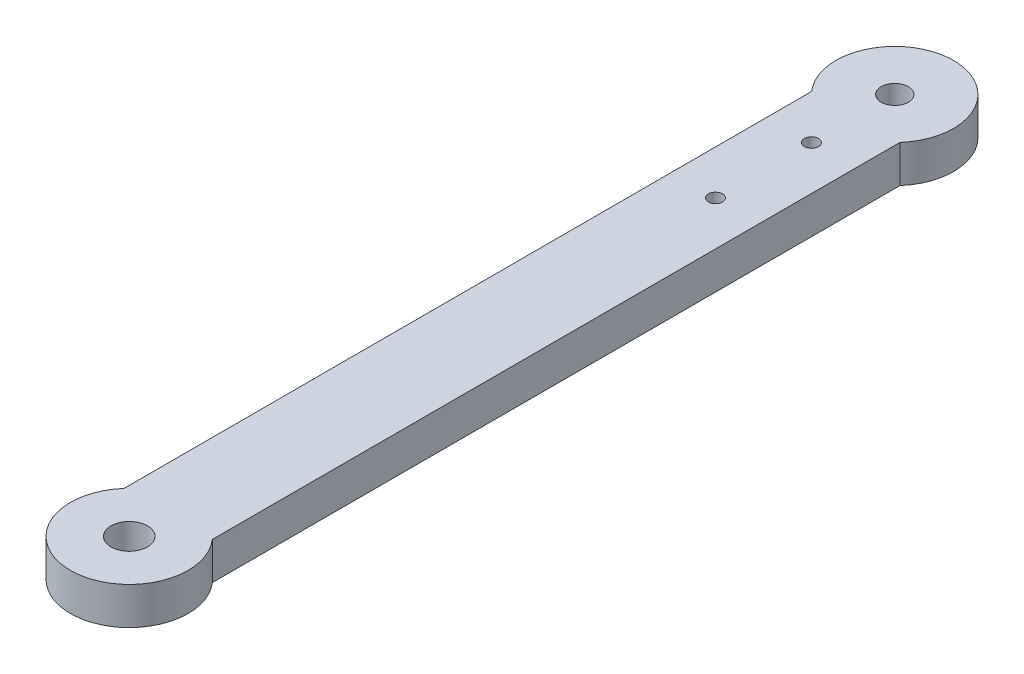
SolidWorks part; units mm, degrees
ref_plane "Front Plane" through (0, 0, 0) normal (0, 0, 1) x (1, 0, 0)
ref_plane "Top Plane" through (0, 0, 0) normal (0, 1, 0) x (1, 0, 0)
ref_plane "Right Plane" through (0, 0, 0) normal (1, 0, 0) x (0, 0, -1)
sketch "Sketch1" plane through (0, 0, 0) normal (0, 1, 0) x (1, 0, 0)
  line L1 (-3.75, -61.6928) -> (-3.75, -3.3072)
  line L4 (3.75, -61.6928) -> (3.75, -3.3072)
  line L5 (-3.75, -3.3072) -> (0, 0) construction
  line L6 (0, 0) -> (3.75, -3.3072) construction
  line L7 (-3.75, -3.3072) -> (3.75, -3.3072) construction
  arc A1 (3.75, -3.3072) -> (-3.75, -3.3072) centre (0, 0) ccw
  arc A2 (-3.75, -61.6928) -> (3.75, -61.6928) centre (0, -65) ccw
  circle A3 centre (0, -65) radius 1.55
  circle A5 centre (0, -7.07) radius 0.6
  circle A6 centre (0, -15.22) radius 0.6
  circle A25 centre (0, 0) radius 1.15
  point P10 (0, 0)
  dimension "D2" = 1.2
  dimension "D3" = 10
  dimension "D6" = 10
  dimension "D5" = 3.1
  dimension "D8" = 2.3
  dimension "D1" = 8.15
  dimension "D4" = 7.5
  dimension "D7" = 65
  dimension "D9" = 7.07
extrude "Boss-Extrude1" add sketch "Sketch1" along normal blind 3.175
